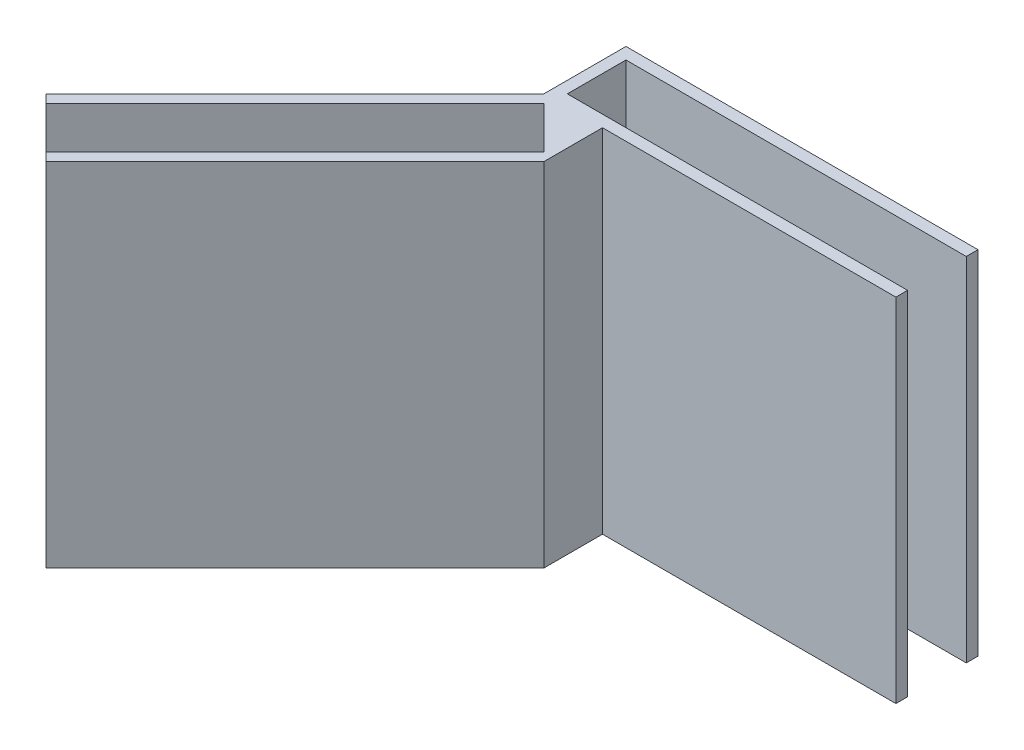
SolidWorks part; units mm, degrees
ref_plane "Front Plane" through (0, 0, 0) normal (0, 0, 1) x (1, 0, 0)
ref_plane "Top Plane" through (0, 0, 0) normal (0, 1, 0) x (1, 0, 0)
ref_plane "Right Plane" through (0, 0, 0) normal (1, 0, 0) x (0, 0, -1)
sketch "Sketch1" plane through (0, 0, 0) normal (0, 0, 1) x (1, 0, 0)
  line L1 (0, 0) -> (30, 0)
  line L2 (0, 0) -> (0, 30)
  line L3 (0, 30) -> (30, 30)
  line L4 (30, 0) -> (30, 30)
  dimension "D1" = 30
  dimension "D2" = 30
extrude "Boss-Extrude1" add sketch "Sketch1" along normal blind 7
shell "Shell1" thickness 1 removed face at (15, 0, 3.5) removed face at (30, 15, 3.5)
sketch "Sketch2" plane through (0, 0, 7) normal (0, 0, 1) x (1, 0, 0)
  line L0 (30, 0) -> (30, 30) construction
  line L1 (0, 30) -> (30, 30)
  line L2 (0, 30) -> (0, 23)
  line L3 (0, 23) -> (30, 23)
  line L4 (30, 30) -> (30, 23)
  dimension "D1" = 7
extrude "Boss-Extrude2" add sketch "Sketch2" along normal blind 30
sketch "Sketch3" plane through (0, 0, 0) normal (-1, 0, 0) x (0, 0, 1)
  line L1 (7, 23) -> (37, 23)
  line L2 (7, 23) -> (7, 30)
  line L3 (7, 30) -> (37, 30)
  line L4 (37, 23) -> (37, 30)
extrude "Boss-Extrude3" add sketch "Sketch3" along normal blind 30
sketch "Sketch4" plane through (0, 23, 0) normal (0, -1, 0) x (1, 0, 0)
  line L4 (-30, 37) -> (0, 7)
  line L5 (0, 7) -> (-30, 7)
  line L6 (-30, 7) -> (-30, 37)
sketch "Sketch5" plane through (0, 0, 7) normal (0, 0, 1) x (1, 0, 0)
  line L0 (0, 23) -> (30, 23) construction
  line L1 (0, 0) -> (5, 0)
  line L2 (0, 0) -> (0, 23)
  line L3 (0, 23) -> (5, 23)
  line L4 (5, 0) -> (5, 23)
  dimension "D1" = 5
extrude "Boss-Extrude4" add sketch "Sketch5" along normal blind 5
sketch "Sketch6" plane through (0, 0, 0) normal (0, -1, 0) x (1, 0, 0)
  line L3 (0, 12) -> (5, 12)
  line L4 (5, 7) -> (0, 7) construction
  line L5 (0, 12) -> (0, 0) construction
  line L6 (5, 12) -> (0, 7)
  line L7 (0, 7) -> (0, 12)
extrude "Cut-Extrude6" cut sketch "Sketch6" against normal blind 23
sketch "Sketch12" plane through (-3.5, 0, 3.5) normal (-0.7071, 0, 0.7071) x (0.7071, 0, 0.7071)
  line L4 (4.9497, 0) -> (12.0208, 0)
  line L5 (12.0208, 0) -> (12.0208, 23)
  line L6 (12.0208, 23) -> (4.9497, 23)
  line L7 (4.9497, 23) -> (4.9497, 0)
  line L8 (4.9497, 0) -> (12.0208, 0)
  line L9 (12.0208, 0) -> (12.0208, 23)
  line L10 (12.0208, 23) -> (4.9497, 23)
  line L11 (4.9497, 23) -> (4.9497, 0)
  dimension "D1" = 0
extrude "Boss-Extrude6" add sketch "Sketch12" along normal blind 30
sketch "Sketch13" plane through (0, 0, 0) normal (0, -1, 0) x (1, 0, 0)
  line L13 (0, 7) -> (5, 12) construction
  line L14 (-19.799, 28.2132) -> (0.7071, 7.7071)
  line L15 (-16.2132, 31.799) -> (4.2929, 11.2929)
  line L16 (4.2929, 11.2929) -> (0.7071, 7.7071)
  line L17 (-19.799, 28.2132) -> (-20.5061, 28.9203)
  line L18 (-21.2132, 28.2132) -> (-16.2132, 33.2132) construction
  line L19 (-16.2132, 31.799) -> (-16.9203, 32.5061)
  line L20 (-16.9203, 32.5061) -> (-20.5061, 28.9203)
extrude "Cut-Extrude7" cut sketch "Sketch13" against normal blind 22
extrude "Cut-Extrude8" cut sketch "Sketch4" against normal blind 22
shell "Shell2" thickness 1 removed face at (0, 26.5, 37)
sketch "Sketch16" plane through (0, 23, 0) normal (0, 1, 0) x (1, 0, 0)
  line L7 (1.4142, -7) -> (1, -7)
  line L8 (1, -7) -> (1, -7.4142)
  line L9 (1, -7.4142) -> (-19.799, -28.2132)
  line L10 (-19.799, -28.2132) -> (-16.2132, -31.799)
  line L11 (-16.2132, -31.799) -> (4, -11.5858)
  line L12 (4, -11.5858) -> (4, -9.5858)
  line L13 (4, -9.5858) -> (1.4142, -7)
  line L14 (1.4142, -7) -> (1, -7)
  line L15 (1, -7) -> (1, -7.4142)
  line L16 (1, -7.4142) -> (-19.799, -28.2132)
  line L17 (-19.799, -28.2132) -> (-16.2132, -31.799)
  line L18 (-16.2132, -31.799) -> (4, -11.5858)
  line L19 (4, -11.5858) -> (4, -9.5858)
  line L20 (4, -9.5858) -> (1.4142, -7)
  dimension "D1" = 0
extrude "Boss-Extrude7" add sketch "Sketch16" along normal blind 1
sketch "Sketch17" plane through (0, 30, 0) normal (0, 1, 0) x (1, 0, 0)
  line L0 (0, -7) -> (30, -7)
  line L1 (30, -7) -> (30, -37)
  line L2 (0, -7) -> (-30, -37)
  line L3 (-30, -37) -> (30, -37)
sketch "Sketch18" plane through (0, 1, 0) normal (0, 1, 0) x (1, 0, 0)
  line L3 (4, -9.5858) -> (4, -7)
  line L4 (4, -7) -> (1.4142, -7)
  line L5 (1.4142, -7) -> (4, -9.5858)
  line L6 (4, -9.5858) -> (4, -7)
  line L7 (4, -7) -> (1.4142, -7)
  line L8 (1.4142, -7) -> (4, -9.5858)
  dimension "D1" = 0
extrude "Boss-Extrude8" add sketch "Sketch18" along normal blind 23
sketch "Sketch19" plane through (30, 0, 0) normal (1, 0, 0) x (0, 0, -1)
  line L0 (-36, 29) -> (-37, 29)
  line L1 (-37, 29) -> (-37, 24)
  line L20 (-36, 24) -> (-37, 24)
  line L21 (-37, 23) -> (-37, 30) construction
  line L30 (-7, 29) -> (-36, 29)
  line L31 (-36, 29) -> (-36, 24)
  line L32 (-36, 24) -> (-7, 24)
  line L33 (-7, 24) -> (-7, 29)
  line L34 (-7, 29) -> (-36, 29)
  line L36 (-36, 24) -> (-7, 24)
  line L37 (-7, 24) -> (-7, 29)
  dimension "D1" = 1
extrude "Cut-Extrude10" cut sketch "Sketch19" against normal blind 1
extrude "Cut-Extrude11" cut sketch "Sketch17" against normal blind 7
sketch "Sketch21" plane through (0, 23, 0) normal (0, 1, 0) x (1, 0, 0)
  line L5 (5, -12) -> (5, -7)
  line L6 (5, -7) -> (0, -7)
  line L7 (0, -7) -> (-21.2132, -28.2132)
  line L8 (-21.2132, -28.2132) -> (-16.2132, -33.2132)
  line L9 (-16.2132, -33.2132) -> (5, -12)
  line L10 (5, -12) -> (5, -7)
  line L11 (5, -7) -> (0, -7)
  line L12 (0, -7) -> (-21.2132, -28.2132)
  line L13 (-21.2132, -28.2132) -> (-16.2132, -33.2132)
  line L14 (-16.2132, -33.2132) -> (5, -12)
  dimension "D1" = 0
extrude "Boss-Extrude9" add sketch "Sketch21" along normal blind 7
sketch "Sketch22" plane through (0, 22, 0) normal (0, -1, 0) x (1, 0, 0)
  line L4 (-16.9203, 32.5061) -> (-20.5061, 28.9203)
  line L5 (-20.5061, 28.9203) -> (0.7071, 7.7071)
  line L6 (0.7071, 7.7071) -> (4.2929, 11.2929)
  line L7 (4.2929, 11.2929) -> (-16.9203, 32.5061)
  line L8 (-16.9203, 32.5061) -> (-20.5061, 28.9203)
  line L9 (-20.5061, 28.9203) -> (0.7071, 7.7071)
  line L10 (0.7071, 7.7071) -> (4.2929, 11.2929)
  line L11 (4.2929, 11.2929) -> (-16.9203, 32.5061)
  dimension "D1" = 0
extrude "Cut-Extrude12" cut sketch "Sketch22" against normal blind 7
sketch "Sketch23" plane through (0, 30, 0) normal (0, 1, 0) x (1, 0, 0)
  line L0 (30, -6) -> (1, -6)
  line L1 (30, -7) -> (30, 0) construction
  line L2 (1, -6) -> (1, -1)
  line L3 (1, -1) -> (30, -1)
  line L4 (30, -7) -> (5, -7) construction
  line L5 (30, 0) -> (0, 0) construction
  line L6 (0, -7) -> (0, 0) construction
  line L7 (30, -6) -> (30, -1)
  dimension "D1" = 1
  dimension "D2" = 1
  dimension "D3" = 1
extrude "Cut-Extrude14" cut sketch "Sketch23" against normal blind 7
sketch "Sketch24" plane through (0, 29, 0) normal (0, -1, 0) x (1, 0, 0)
  line L4 (4.2929, 11.2929) -> (-16.9203, 32.5061)
  line L5 (-16.9203, 32.5061) -> (-20.5061, 28.9203)
  line L6 (-20.5061, 28.9203) -> (0.7071, 7.7071)
  line L7 (0.7071, 7.7071) -> (4.2929, 11.2929)
  line L8 (4.2929, 11.2929) -> (-16.9203, 32.5061)
  line L9 (-16.9203, 32.5061) -> (-20.5061, 28.9203)
  line L10 (-20.5061, 28.9203) -> (0.7071, 7.7071)
  line L11 (0.7071, 7.7071) -> (4.2929, 11.2929)
  dimension "D1" = 0
extrude "Cut-Extrude15" cut sketch "Sketch24" against normal blind 7
